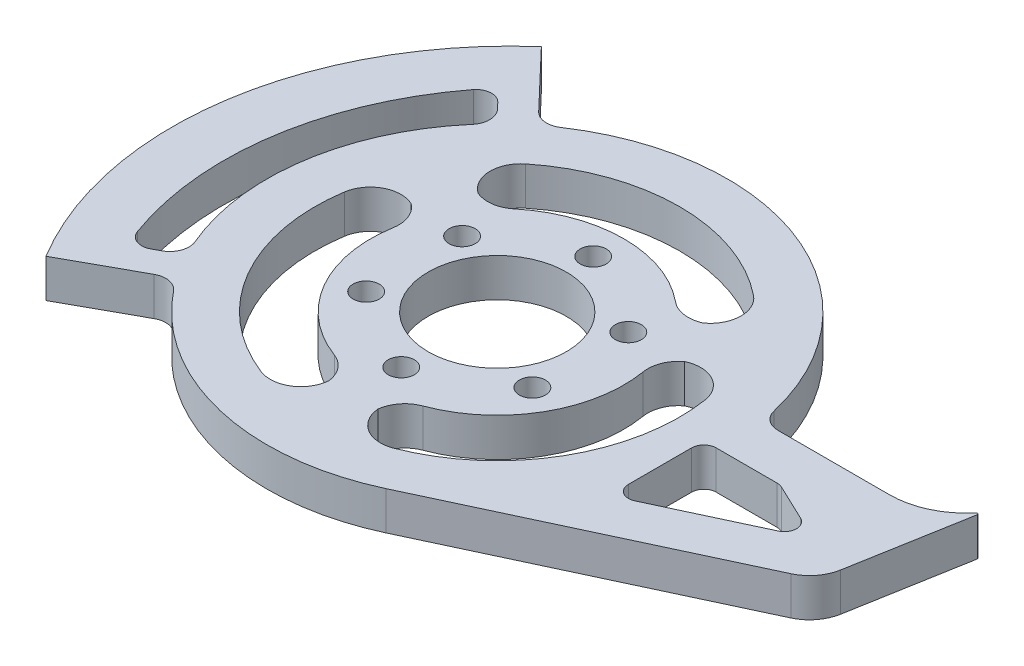
SolidWorks part; units mm, degrees
material "AISI Type A2 Tool Steel"
ref_plane "Front Plane" through (0, 0, 0) normal (0, 0, 1) x (1, 0, 0)
ref_plane "Top Plane" through (0, 0, 0) normal (0, 1, 0) x (1, 0, 0)
ref_plane "Right Plane" through (0, 0, 0) normal (1, 0, 0) x (0, 0, -1)
other "Center of Mass"
other "Bounding Box"
ref_plane "Default Plane" through (-8.9266, -12.7485, 0) normal (-0.1736, 0.9848, 0) x (0.9848, 0.1736, 0)
sketch "Sketch1" plane through (0, 0, 0) normal (0, 1, 0) x (1, 0, 0)
  line B0 (31.1591, 5.9433) -> (29.0547, 5.5565)
  line B1 (26.0289, -14.0552) -> (27.9189, -15.0583)
  line B2 (27.7728, 4.2372) -> (25.2042, -12.4109)
  line B3 (-45.8426, -24.1464) -> (-36.4371, -18.9694)
  line B4 (-29.0253, 29.0694) -> (-36.4331, 36.8405)
  line B5 (52.9152, -8.1642) -> (47.6562, -0.9862)
  line B6 (45.7373, -13.4232) -> (52.9152, -8.1642)
  line B7 (-2.3359, -29.5358) -> (-2.3709, -28.5547)
  line B8 (-6.3457, -27.9414) -> (-6.6748, -28.8663)
  line B9 (-22.2418, -12.44) -> (-7.3488, -24.4018)
  line B10 (-26.7467, -12.7449) -> (-25.9145, -12.2241)
  line B11 (-27.3708, -8.4752) -> (-28.3364, -8.6526)
  line B12 (-21.8942, 13.042) -> (-24.807, -5.8366)
  line B13 (-24.4107, 16.7909) -> (-23.5436, 16.3306)
  line B14 (-21.0251, 19.4663) -> (-21.6616, 20.2137)
  line B15 (0.3476, 25.482) -> (-17.4581, 18.5652)
  line B16 (2.3359, 29.5358) -> (2.3709, 28.5547)
  line B17 (6.3457, 27.9414) -> (6.6748, 28.8663)
  line B18 (22.2418, 12.44) -> (7.3488, 24.4018)
  line B19 (26.7467, 12.7449) -> (25.9145, 12.2241)
  line B20 (27.3708, 8.4752) -> (28.3364, 8.6526)
  line B21 (21.8942, -13.042) -> (24.807, 5.8366)
  line B22 (24.4107, -16.7909) -> (23.5436, -16.3306)
  line B23 (21.0251, -19.4663) -> (21.6616, -20.2137)
  line B24 (-0.3476, -25.482) -> (17.4581, -18.5652)
  line B25 (20.7267, -24.0129) -> (19.3394, -22.3839)
  line B26 (0.8423, -29.5693) -> (0.9185, -31.7076)
  line B27 (17.5559, -21.9333) -> (1.8539, -28.0329)
  line B28 (10.4325, 29.9563) -> (9.7153, 27.9404)
  line B29 (25.1866, 15.5141) -> (27.0003, 16.6493)
  line B30 (10.2168, 26.1705) -> (23.3502, 15.622)
  line B31 (-10.4325, -29.9563) -> (-9.7153, -27.9404)
  line B32 (-25.1866, -15.5141) -> (-27.0003, -16.6493)
  line B33 (-10.2168, -26.1705) -> (-23.3502, -15.622)
  line B34 (-0.8423, 29.5693) -> (-0.9185, 31.7076)
  line B35 (-17.5559, 21.9333) -> (-1.8539, 28.0329)
  line B36 (-20.7267, 24.0129) -> (-19.3394, 22.3839)
  line B37 (-31.1591, -5.9433) -> (-29.0547, -5.5565)
  line B38 (-26.0289, 14.0552) -> (-27.9189, 15.0583)
  line B39 (-27.7728, -4.2372) -> (-25.2042, 12.4109)
  line B40 (-25.2564, 32.1101) -> (-39.3478, 46.8924)
  line B41 (-51.6515, -32.8524) -> (-33.7603, -23.0048)
  line B42 (16.1018, -34.5303) -> (61.8073, -13.2175)
  line B43 (65.3772, -8.5651) -> (68.9058, 11.4462)
  line B44 (58.6548, 6.2434) -> (40.1861, 6.2434)
  arc B45 (42.6375, -6.5784) -> (45.7373, -13.4232) centre (43.4684, -10.3264) ccw
  arc B46 (33.0185, 4.6011) -> (31.1591, 5.9433) centre (31.4462, 4.382) ccw
  arc B47 (30.0963, -14.3389) -> (33.0185, 4.6011) centre (0, 0) ccw
  arc B48 (27.9189, -15.0583) -> (30.0963, -14.3389) centre (28.6631, -13.6561) ccw
  arc B49 (25.2042, -12.4109) -> (26.0289, -14.0552) centre (26.7731, -12.653) ccw
  arc B50 (29.0547, 5.5565) -> (27.7728, 4.2372) centre (29.3417, 3.9952) ccw
  arc B51 (47.6562, -0.9862) -> (42.6375, -6.5784) centre (44.5594, -3.2551) ccw
  arc B52 (-0.3476, -25.482) -> (-2.3709, -28.5547) centre (0.8021, -28.4415) ccw
  arc B53 (-6.6748, -28.8663) -> (-2.3359, -29.5358) centre (-4.5693, -29.6154) ccw
  arc B54 (-6.3457, -27.9414) -> (-7.3488, -24.4018) centre (-9.337, -26.8772) ccw
  arc B55 (-22.2418, -12.44) -> (-25.9145, -12.2241) centre (-24.2301, -14.9154) ccw
  arc B56 (-28.3364, -8.6526) -> (-26.7467, -12.7449) centre (-27.9323, -10.8506) ccw
  arc B57 (-27.3708, -8.4752) -> (-24.807, -5.8366) centre (-27.9448, -5.3525) ccw
  arc B58 (-21.8942, 13.042) -> (-23.5436, 16.3306) centre (-25.0321, 13.5262) ccw
  arc B59 (-21.6616, 20.2137) -> (-24.4107, 16.7909) centre (-23.363, 18.7648) ccw
  arc B60 (-21.0251, 19.4663) -> (-17.4581, 18.5652) centre (-18.6078, 21.5247) ccw
  arc B61 (0.3476, 25.482) -> (2.3709, 28.5547) centre (-0.8021, 28.4415) ccw
  arc B62 (6.6748, 28.8663) -> (2.3359, 29.5358) centre (4.5693, 29.6154) ccw
  arc B63 (6.3457, 27.9414) -> (7.3488, 24.4018) centre (9.337, 26.8772) ccw
  arc B64 (22.2418, 12.44) -> (25.9145, 12.2241) centre (24.2301, 14.9154) ccw
  arc B65 (28.3364, 8.6526) -> (26.7467, 12.7449) centre (27.9323, 10.8506) ccw
  arc B66 (27.3708, 8.4752) -> (24.807, 5.8366) centre (27.9448, 5.3525) ccw
  arc B67 (21.8942, -13.042) -> (23.5436, -16.3306) centre (25.0321, -13.5262) ccw
  arc B68 (21.6616, -20.2137) -> (24.4107, -16.7909) centre (23.363, -18.7648) ccw
  arc B69 (21.0251, -19.4663) -> (17.4581, -18.5652) centre (18.6078, -21.5247) ccw
  arc B70 (-28.914, 24.8111) -> (-35.0475, -14.9427) centre (0, 0) ccw
  arc B71 (-36.4371, -18.9694) -> (-35.0475, -14.9427) centre (-37.9681, -16.1879) ccw
  arc B72 (-50.2679, -22.6701) -> (-45.8426, -24.1464) centre (-47.3736, -21.3649) ccw
  arc B73 (-41.0975, 36.7667) -> (-50.2679, -22.6701) centre (0, 0) ccw
  arc B74 (-36.4331, 36.8405) -> (-41.0975, 36.7667) centre (-38.7312, 34.6498) ccw
  arc B75 (-28.914, 24.8111) -> (-29.0253, 29.0694) centre (-31.3235, 26.8787) ccw
  arc B76 (20.4939, -26.2943) -> (20.7267, -24.0129) centre (19.518, -25.0422) ccw
  arc B77 (2.6303, -33.2336) -> (20.4939, -26.2943) centre (0, 0) ccw
  arc B78 (0.9185, -31.7076) -> (2.6303, -33.2336) centre (2.505, -31.651) ccw
  arc B79 (1.8539, -28.0329) -> (0.8423, -29.5693) centre (2.4288, -29.5127) ccw
  arc B80 (19.3394, -22.3839) -> (17.5559, -21.9333) centre (18.1308, -23.4131) ccw
  arc B81 (12.5246, 30.8954) -> (10.4325, 29.9563) centre (11.9282, 29.4242) ccw
  arc B82 (27.466, 18.8947) -> (12.5246, 30.8954) centre (0, 0) ccw
  arc B83 (27.0003, 16.6493) -> (27.466, 18.8947) centre (26.1581, 17.9949) ccw
  arc B84 (23.3502, 15.622) -> (25.1866, 15.5141) centre (24.3444, 16.8597) ccw
  arc B85 (9.7153, 27.9404) -> (10.2168, 26.1705) centre (11.211, 27.4082) ccw
  arc B86 (-12.5246, -30.8954) -> (-10.4325, -29.9563) centre (-11.9282, -29.4242) ccw
  arc B87 (-27.466, -18.8947) -> (-12.5246, -30.8954) centre (0, 0) ccw
  arc B88 (-27.0003, -16.6493) -> (-27.466, -18.8947) centre (-26.1581, -17.9949) ccw
  arc B89 (-23.3502, -15.622) -> (-25.1866, -15.5141) centre (-24.3444, -16.8597) ccw
  arc B90 (-9.7153, -27.9404) -> (-10.2168, -26.1705) centre (-11.211, -27.4082) ccw
  arc B91 (-2.6303, 33.2336) -> (-20.4939, 26.2943) centre (0, 0) ccw
  arc B92 (-0.9185, 31.7076) -> (-2.6303, 33.2336) centre (-2.505, 31.651) ccw
  arc B93 (-1.8539, 28.0329) -> (-0.8423, 29.5693) centre (-2.4288, 29.5127) ccw
  arc B94 (-19.3394, 22.3839) -> (-17.5559, 21.9333) centre (-18.1308, 23.4131) ccw
  arc B95 (-20.4939, 26.2943) -> (-20.7267, 24.0129) centre (-19.518, 25.0422) ccw
  arc B96 (-33.0185, -4.6011) -> (-31.1591, -5.9433) centre (-31.4462, -4.382) ccw
  arc B97 (-30.0963, 14.3389) -> (-33.0185, -4.6011) centre (0, 0) ccw
  arc B98 (-27.9189, 15.0583) -> (-30.0963, 14.3389) centre (-28.6631, 13.6561) ccw
  arc B99 (-25.2042, 12.4109) -> (-26.0289, 14.0552) centre (-26.7731, 12.653) ccw
  arc B100 (-29.0547, -5.5565) -> (-27.7728, -4.2372) centre (-29.3417, -3.9952) ccw
  arc B101 (-39.3478, 46.8924) -> (-51.6515, -32.8524) centre (0, 0) ccw
  arc B102 (-29.7495, -23.8029) -> (-33.7603, -23.0048) centre (-32.2291, -25.7868) ccw
  arc B103 (-29.7495, -23.8029) -> (16.1018, -34.5303) centre (0, 0) ccw
  arc B104 (61.8073, -13.2175) -> (65.3772, -8.5651) centre (59.1237, -7.4624) ccw
  arc B105 (58.6548, 6.2434) -> (68.9058, 11.4462) centre (58.6548, 18.9434) ccw
  arc B106 (37.0948, 8.6939) -> (40.1861, 6.2434) centre (40.1861, 9.4184) ccw
  arc B107 (37.0948, 8.6939) -> (-21.1923, 31.6622) centre (0, 0) ccw
  arc B108 (-25.2564, 32.1101) -> (-21.1923, 31.6622) centre (-22.9583, 34.3008) ccw
sketch_block_instance "Wepon-1"
sketch_block "Wepon"
extrude "Boss-Extrude1" add sketch "Sketch1" along normal blind 6.35
sketch "Sketch2" plane through (0, 6.35, 0) normal (0, 1, 0) x (1, 0, 0)
  line L0 (45.7373, -13.4232) -> (52.9152, -8.1642)
  line L1 (52.9152, -8.1642) -> (47.6562, -0.9862)
  circle A0 centre (0, 0) radius 38.1
  arc A1 (42.6375, -6.5784) -> (45.7373, -13.4232) centre (43.4684, -10.3264) ccw
  arc A2 (42.6375, -6.5784) -> (47.6562, -0.9862) centre (44.5594, -3.2551) cw
extrude "Boss-Extrude2" add sketch "Sketch2" against normal up to surface (6.35 mm away) up to face at (-28.9513, 0, -4.4668)
sketch "Sketch5" plane through (0, 6.35, 0) normal (0, 1, 0) x (1, 0, 0)
  arc B0 (-18.8515, 23.5457) -> (18.8515, 23.5457) centre (0, 0) cw
  arc B1 (18.8515, 23.5457) -> (18.5756, 15.4086) centre (15.6765, 19.5801) cw
  arc B2 (18.5756, 15.4086) -> (13.3403, 16.1601) centre (16.5743, 20.0777) cw
  arc B3 (13.3403, 16.1601) -> (-13.3403, 16.1601) centre (0, 0) ccw
  arc B4 (-13.3403, 16.1601) -> (-18.5756, 15.4086) centre (-16.5743, 20.0777) cw
  arc B5 (-18.5756, 15.4086) -> (-18.8515, 23.5457) centre (-15.6765, 19.5801) cw
  arc B6 (-20.6652, 3.473) -> (-22.632, 8.3827) centre (-25.6749, 4.3149) ccw
  arc B7 (-22.632, 8.3827) -> (-29.8169, 4.553) centre (-24.7951, 3.7862) ccw
  arc B8 (-29.8169, 4.553) -> (-10.9654, -28.0987) centre (0, 0) ccw
  arc B9 (-10.9654, -28.0987) -> (-4.0564, -23.7912) centre (-9.1186, -23.3663) ccw
  arc B10 (-4.0564, -23.7912) -> (-7.3249, -19.6331) centre (-9.1007, -24.3926) ccw
  arc B11 (-7.3249, -19.6331) -> (-20.6652, 3.473) centre (0, 0) cw
  arc B12 (7.3249, -19.6331) -> (4.0564, -23.7912) centre (9.1007, -24.3926) ccw
  arc B13 (4.0564, -23.7912) -> (10.9654, -28.0987) centre (9.1186, -23.3663) ccw
  arc B14 (10.9654, -28.0987) -> (29.8169, 4.553) centre (0, 0) ccw
  arc B15 (29.8169, 4.553) -> (22.632, 8.3827) centre (24.7951, 3.7862) ccw
  arc B16 (22.632, 8.3827) -> (20.6652, 3.473) centre (25.6749, 4.3149) ccw
  arc B17 (20.6652, 3.473) -> (7.3249, -19.6331) centre (0, 0) cw
  circle B18 centre (0, 0) radius 11.43
  circle B19 centre (13.7482, 7.9375) radius 2.159
  circle B20 centre (0, 15.875) radius 2.159
  circle B21 centre (-13.7482, 7.9375) radius 2.159
  circle B22 centre (-13.7482, -7.9375) radius 2.159
  circle B23 centre (0, -15.875) radius 2.159
  circle B24 centre (13.7482, -7.9375) radius 2.159
sketch_block_instance "Wepon for Pulley-1"
sketch_block "Wepon for Pulley"
extrude "Cut-Extrude2" cut sketch "Sketch5" against normal through all both and the other way through all
sketch "Sketch6" plane through (0, 6.35, 0) normal (0, 1, 0) x (1, 0, 0)
  line L0 (-25.2564, 32.1101) -> (-39.3478, 46.8924) construction
  line L1 (-51.6515, -32.8524) -> (-33.7603, -23.0048) construction
  line L2 (-39.3478, 46.8924) -> (-28.6284, 35.6474)
  line L3 (-51.6515, -32.8524) -> (-38.0412, -25.3611)
  arc A0 (-28.6284, 35.6474) -> (-38.0412, -25.3611) centre (6.2325, -0.9616) ccw
  arc A1 (-39.3478, 46.8924) -> (-51.6515, -32.8524) centre (0, 0) ccw
  arc A2 (-34.3418, 41.6409) -> (-45.2954, -29.3539) centre (2.4887, -0.384) ccw
  line M29 (-36.4371, -18.9694) -> (-45.8426, -24.1464)
  arc M30 (-45.8426, -24.1464) -> (-50.2679, -22.6701) centre (-47.3736, -21.3649) cw
  arc M31 (-50.2679, -22.6701) -> (-41.0975, 36.7667) centre (0, 0) cw
  arc M32 (-41.0975, 36.7667) -> (-36.4331, 36.8405) centre (-38.7312, 34.6498) cw
  line M33 (-36.4331, 36.8405) -> (-29.0253, 29.0694)
  arc M37 (-39.3478, 46.8924) -> (-51.6515, -32.8524) centre (0, 0) ccw
  line M38 (-51.6515, -32.8524) -> (-33.7603, -23.0048)
  dimension "D3" = 50.5519
  dimension "D4" = 61.214
  dimension "D7" = 55.88
  dimension "D1" = 45.72
  dimension "D2" = 45.72
  dimension "D5" = 8.2804
  dimension "D6" = 8.2804
extrude "Cut-Extrude3" cut sketch "Sketch6" against normal through all both and the other way through all contours A2 L2 M37 M38 M29 M30 M31 M32 M33 region at (-37.4539, 6.35, -43.686)
extrude "Boss-Extrude3" add sketch "Sketch6<3>" against normal up to surface (6.35 mm away) contours A2 A0 M33 M29 region at (-44.4956, 6.35, -6.8651) up to face at (0, 0, -20.0053)
sketch "Sketch6<3>" plane through (0, 6.35, 0) normal (0, 1, 0) x (1, 0, 0) same geometry as "Sketch6"
fillet "Fillet1" radius 2.54 2 edges at (-40.1683, 3.175, 21.0231) (-31.964, 3.175, -32.1522)
sketch "Sketch8" plane through (0, 6.35, 0) normal (0, 1, 0) x (1, 0, 0)
  line L0 (16.1018, -34.5303) -> (61.8073, -13.2175) construction
  line L1 (35.56, -1.3766) -> (48.1551, -1.3766)
  line L2 (48.1551, -1.3766) -> (58.5574, -6.3252)
  line L3 (58.5574, -6.3252) -> (35.56, -17.0491)
  line L4 (35.56, -17.0491) -> (35.56, -1.3766)
  line L6 (58.6548, 6.2434) -> (40.1861, 6.2434) construction
  arc A0 (58.6548, 6.2434) -> (68.9058, 11.4462) centre (58.6548, 18.9434) ccw construction
  dimension "D1" = 7.62
  dimension "D2" = 7.62
  dimension "D3" = 35.56
  dimension "D4" = 22.86
  dimension "D5" = 11.5193
extrude "Cut-Extrude4" cut sketch "Sketch8" against normal through all
fillet "Fillet2" radius 2.032 4 edges at (35.56, 3.175, 17.0491) (35.56, 3.175, 1.3766) (58.5574, 3.175, 6.3252)
fillet "Fillet3" radius 0.2032 1 edges at (68.9058, 3.175, -11.4462)
